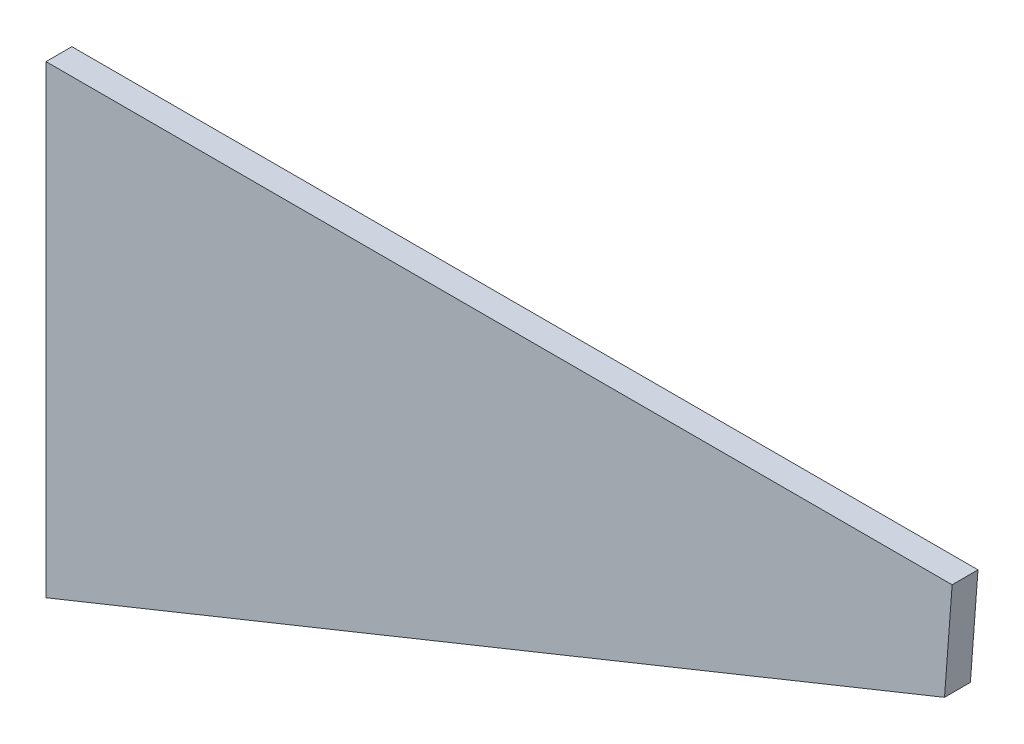
SolidWorks part; units mm, degrees
ref_plane "Front Plane" through (0, 0, 0) normal (0, 0, 1) x (1, 0, 0)
ref_plane "Top Plane" through (0, 0, 0) normal (0, 1, 0) x (1, 0, 0)
ref_plane "Right Plane" through (0, 0, 0) normal (1, 0, 0) x (0, 0, -1)
sketch "Sketch1" plane through (0, 0, 0) normal (0, 0, 1) x (1, 0, 0)
  line L4 (2683.51, 6983.73) -> (2683.51, 6641.7419)
  line L5 (2683.51, 6641.7419) -> (3345.2809, 6909.1147)
  line L6 (3345.2809, 6909.1147) -> (3350.88, 6983.73)
  line L7 (3350.88, 6983.73) -> (2683.51, 6983.73)
  line L8 (2683.51, 6983.73) -> (2683.51, 6641.7419)
  line L9 (2683.51, 6641.7419) -> (3345.2809, 6909.1147)
  line L10 (3345.2809, 6909.1147) -> (3350.88, 6983.73)
  line L11 (3350.88, 6983.73) -> (2683.51, 6983.73)
  dimension "D1" = 0
extrude "Boss-Extrude1" add sketch "Sketch1" along normal blind 19.05
